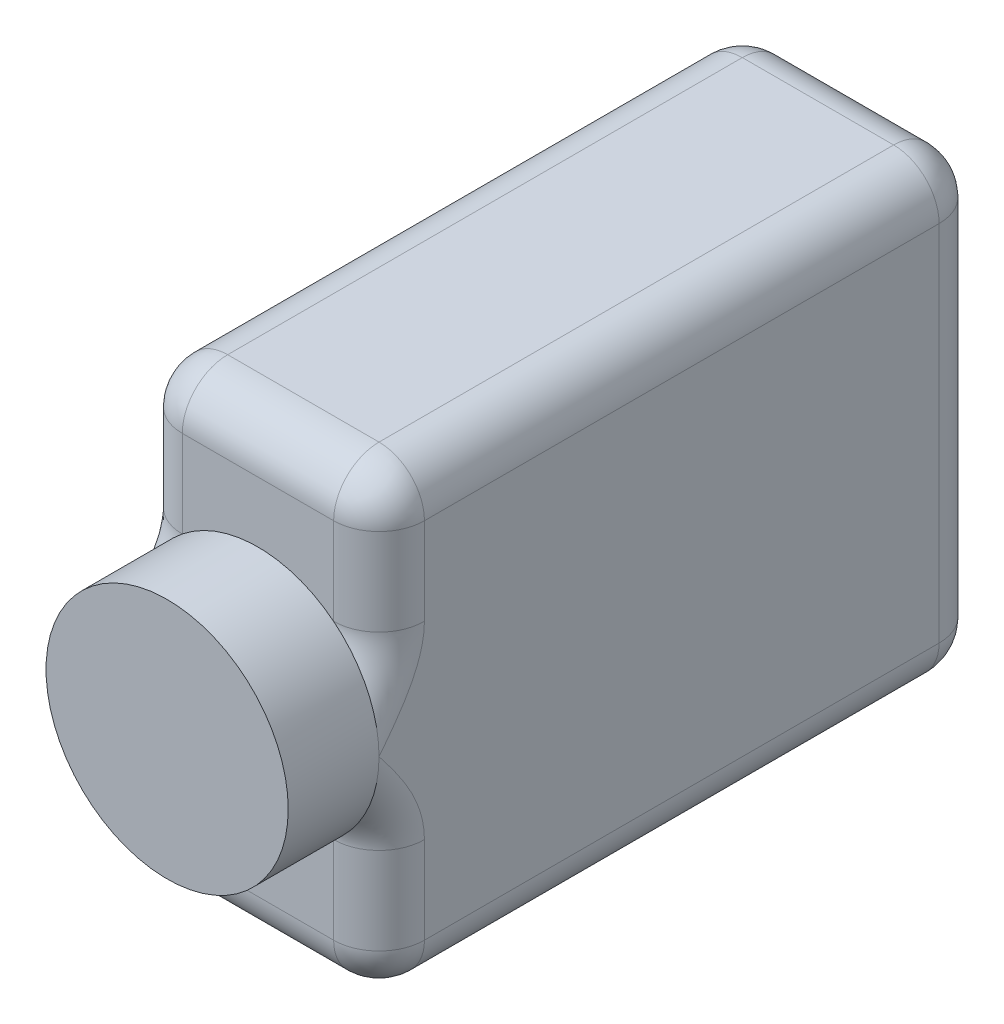
SolidWorks part; units mm, degrees
ref_plane "Front Plane" through (0, 0, 0) normal (0, 0, 1) x (1, 0, 0)
ref_plane "Top Plane" through (0, 0, 0) normal (0, 1, 0) x (1, 0, 0)
ref_plane "Right Plane" through (0, 0, 0) normal (1, 0, 0) x (0, 0, -1)
sketch "Sketch1" plane through (0, 0, 0) normal (0, 0, 1) x (1, 0, 0)
  line L1 (-83.8015, -5.9708) -> (-43.1615, -5.9708)
  line L2 (-83.8015, -5.9708) -> (-83.8015, 70.2292)
  line L3 (-83.8015, 70.2292) -> (-43.1615, 70.2292)
  line L4 (-43.1615, -5.9708) -> (-43.1615, 70.2292)
  line L5 (-83.8015, -5.9708) -> (-43.1615, 70.2292) construction
  line L6 (-83.8015, 70.2292) -> (-43.1615, -5.9708) construction
  circle A0 centre (-63.4815, 32.1292) radius 20.32
  dimension "D1" = 76.2
  dimension "D2" = 40.64
extrude "Boss-Extrude1" add sketch "Sketch1" along normal blind 15.24 contours A0
extrude "Boss-Extrude2" add sketch "Sketch1<3>" against normal blind 101.6 contours A0 L4 L3 L2 | A0 L2 L1 L4 | A0 region at (-63.4815, 5.5641, 0) region at (-63.4815, 58.6943, 0) region at (-63.4815, 32.1292, 0)
sketch "Sketch1<3>" plane through (0, 0, 0) normal (0, 0, 1) x (1, 0, 0) same geometry as "Sketch1"
fillet "Fillet1" radius 7.62 4 edges at (-43.1615, 13.0792, 0) (-63.4815, 70.2292, 0) (-43.1615, 51.1792, 0) (-43.1615, 70.2292, -50.8)
fillet "Fillet2" radius 7.62 6 edges at (-83.8015, 13.0792, 0) (-83.8015, -5.9708, -50.8) (-83.8015, 32.1292, -101.6) (-83.8015, 70.2292, -54.61) (-83.8015, 67.9974, -2.2318) (-83.8015, 47.3692, 0)
fillet "Fillet4" radius 7.62 6 edges at (-81.5696, 67.9974, -99.3682) (-81.5696, -3.739, -99.3682) (-43.1615, 28.3192, -101.6) (-45.3933, 67.9974, -101.6) (-63.4815, 70.2292, -101.6) (-59.6715, -5.9708, -101.6)
fillet "Fillet5" radius 7.62 5 edges at (-45.3933, -3.739, -99.3682) (-81.5696, -3.739, -2.2318) (-63.4815, -5.9708, 0) (-45.3933, -5.9708, -2.2318) (-43.1615, -5.9708, -50.8)
